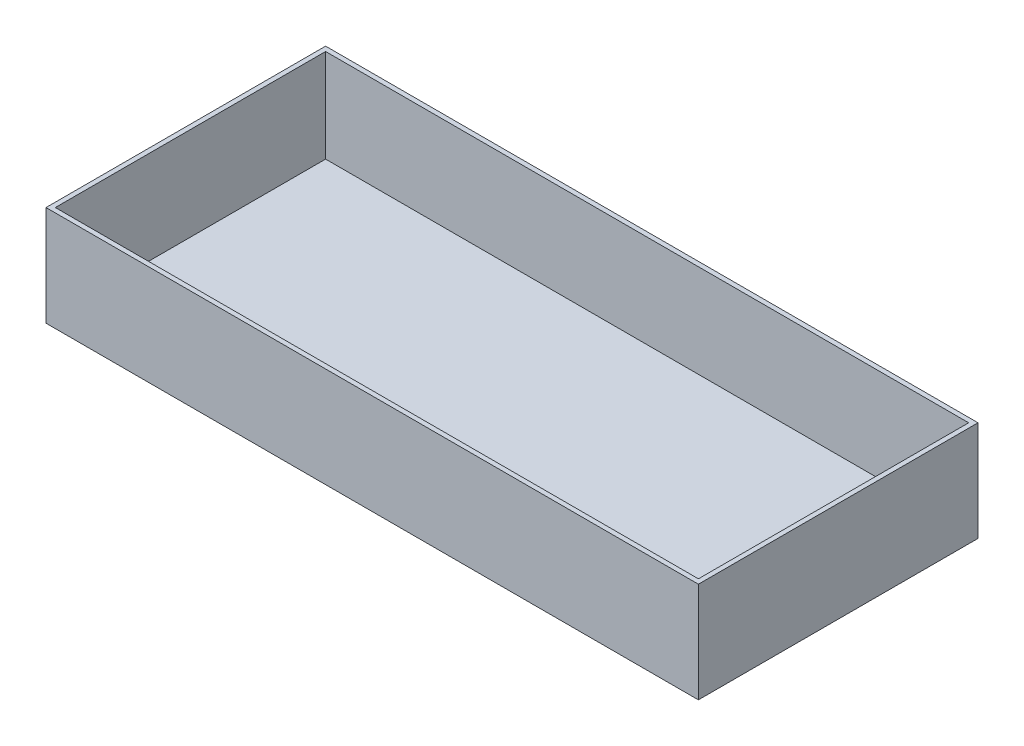
SolidWorks part; units mm, degrees
ref_plane "Front" through (0, 0, 0) normal (0, 0, 1) x (1, 0, 0)
ref_plane "Top" through (0, 0, 0) normal (0, 1, 0) x (1, 0, 0)
ref_plane "Right" through (0, 0, 0) normal (1, 0, 0) x (0, 0, -1)
sketch "Sketch1" plane through (0, 0, 0) normal (0, 1, 0) x (1, 0, 0)
  line L1 (0, 0) -> (280, 0)
  line L2 (0, 0) -> (0, -120)
  line L3 (0, -120) -> (280, -120)
  line L4 (280, 0) -> (280, -120)
  dimension "D1" = 280
  dimension "D2" = 120
extrude "Boss-Extrude1" add sketch "Sketch1" along normal blind 3
sketch "Sketch2" plane through (0, 3, 0) normal (0, 1, 0) x (1, 0, 0)
  line L0 (2, -2) -> (2, -118)
  line L1 (0, 0) -> (280, 0)
  line L2 (0, 0) -> (0, -120)
  line L3 (0, -120) -> (280, -120)
  line L4 (280, 0) -> (280, -120)
  line L5 (2, -118) -> (278, -118)
  line L6 (278, -2) -> (278, -118)
  line L7 (2, -2) -> (278, -2)
  dimension "D1" = 2
extrude "Boss-Extrude2" add sketch "Sketch2" along normal blind 40
